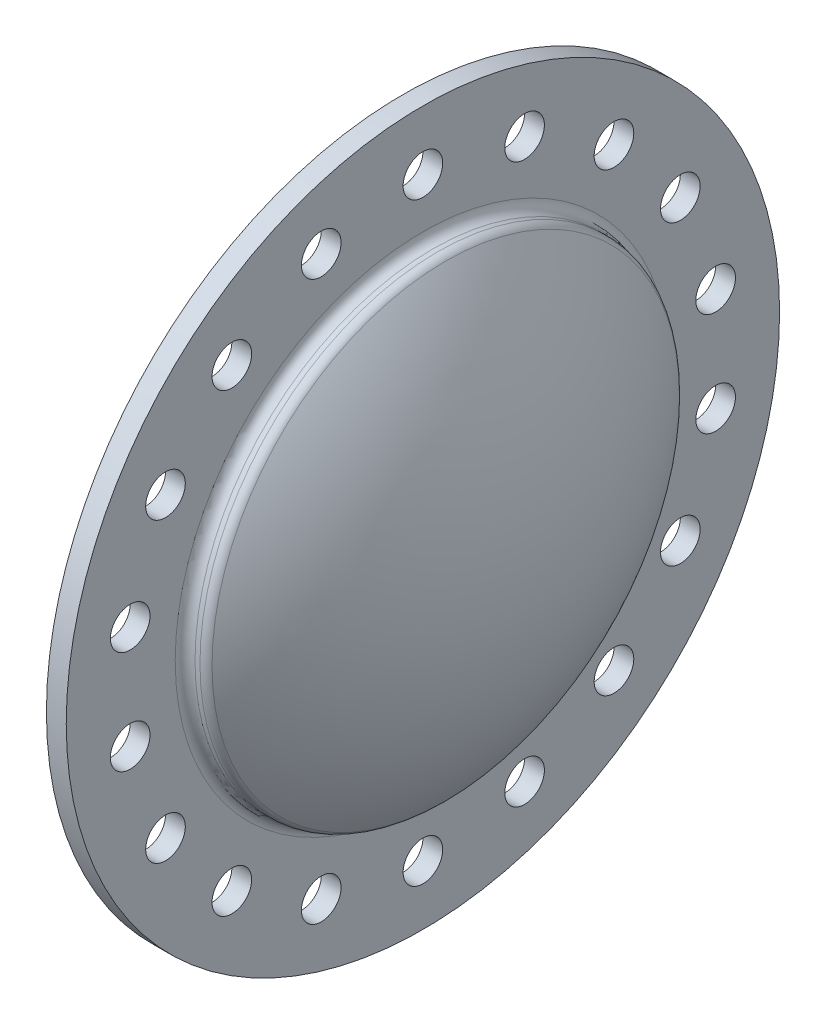
SolidWorks part; units mm, degrees
ref_plane "Front Plane" through (0, 0, 0) normal (0, 0, 1) x (1, 0, 0)
ref_plane "Top Plane" through (0, 0, 0) normal (0, 1, 0) x (1, 0, 0)
ref_plane "Right Plane" through (0, 0, 0) normal (1, 0, 0) x (0, 0, -1)
sketch "Sketch1" plane through (0, 0, 0) normal (1, 0, 0) x (0, 0, -1)
  circle A0 centre (0, 0) radius 75 construction
  circle A1 centre (0, 75) radius 5
  circle A2 centre (25.6516, 70.4773) radius 5
  circle A3 centre (48.2093, 57.454) radius 5
  circle A4 centre (64.9524, 37.5009) radius 5
  circle A5 centre (73.8614, 13.0246) radius 5
  circle A6 centre (73.8618, -13.0226) radius 5
  circle A7 centre (64.9534, -37.4991) radius 5
  circle A8 centre (48.2108, -57.4527) radius 5
  circle A9 centre (25.6535, -70.4766) radius 5
  circle A10 centre (0.002, -75) radius 5
  circle A11 centre (-25.6496, -70.4773) radius 5
  circle A12 centre (-48.2073, -57.454) radius 5
  circle A13 centre (-64.9504, -37.5009) radius 5
  circle A14 centre (-73.8594, -13.0246) radius 5
  circle A15 centre (-73.8598, 13.0226) radius 5
  circle A16 centre (-64.9514, 37.4991) radius 5
  circle A17 centre (-48.2088, 57.4527) radius 5
  circle A18 centre (-25.6515, 70.4766) radius 5
  circle A19 centre (0, 0) radius 90
  circle A20 centre (0, 0) radius 60
  point P42 (0.001, 0)
  dimension "D1" = 150
  dimension "D2" = 10
  dimension "D4" = 180
  dimension "D5" = 120
  dimension "D3" = 18
extrude "Boss-Extrude1" add sketch "Sketch1" along normal blind 5
sketch "Sketch2" plane through (5, 0, 0) normal (1, 0, 0) x (0, 0, -1)
  circle A0 centre (0, 0) radius 60
extrude "Boss-Extrude2" add sketch "Sketch2" along normal blind 5 separate body
dome "Dome1" faces to dome 1 distance 20 reverse direction no elliptical dome no face at (10, 0, -60) parameters "D1"=20
sketch "Sketch3" plane through (5, 0, 0) normal (-1, 0, 0) x (0, 0, 1)
  circle A1 centre (0, 0) radius 60
  circle A2 centre (0, 0) radius 60
  dimension "D1" = 0
extrude "Boss-Extrude3" add sketch "Sketch3" along normal up to surface (5 mm away) up to face at (0, 0, -90)
fillet "Fillet2" radius 2.5 2 edges at (10, 0, -60) (5, 0, -60)
